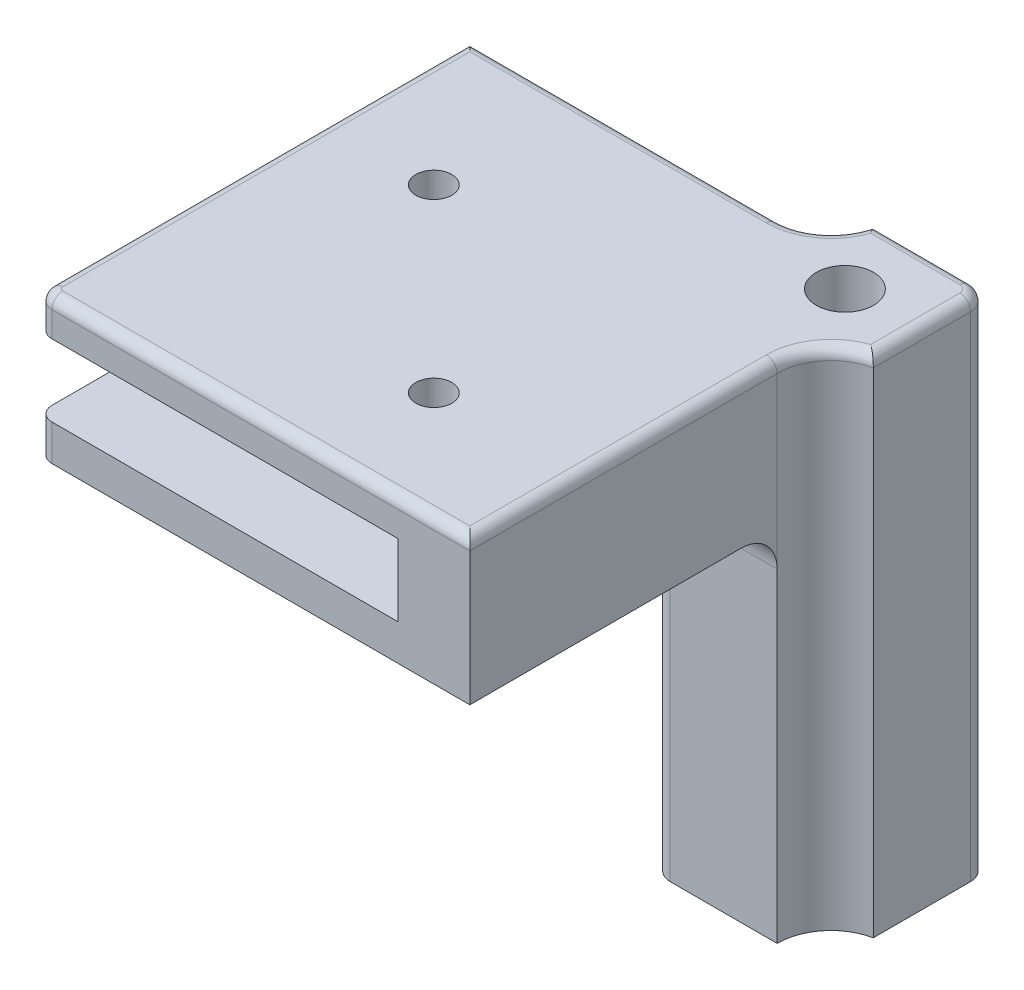
SolidWorks part; units mm, degrees
ref_plane "Front Plane" through (0, 0, 0) normal (0, 0, 1) x (1, 0, 0)
ref_plane "Top Plane" through (0, 0, 0) normal (0, 1, 0) x (1, 0, 0)
ref_plane "Right Plane" through (0, 0, 0) normal (1, 0, 0) x (0, 0, -1)
sketch "Sketch1" plane through (0, 0, 0) normal (0, 1, 0) x (1, 0, 0)
  line L1 (0, 0) -> (76.2, 0)
  line L2 (0, 0) -> (0, 76.2)
  line L3 (0, 76.2) -> (76.2, 76.2)
  line L4 (76.2, 0) -> (76.2, 76.2)
  dimension "D1" = 76.2
  dimension "D2" = 76.2
extrude "Boss-Extrude1" add sketch "Sketch1" along normal mid plane 25.4
sketch "Sketch3" plane through (0, 0, 0) normal (0, 1, 0) x (1, 0, 0)
  line L1 (63.5, 63.5) -> (0, 63.5)
  line L2 (63.5, 63.5) -> (63.5, 0)
  line L3 (63.5, 0) -> (0, 0)
  line L4 (0, 63.5) -> (0, 0)
  dimension "D1" = 63.5
  dimension "D2" = 63.5
extrude "Cut-Extrude1" cut sketch "Sketch3" against normal mid plane 12.7
sketch "Sketch4" plane through (0, 0, 0) normal (0, 1, 0) x (1, 0, 0)
  line L6 (76.2, 0) -> (76.2, 76.2) construction
  line L10 (0, 76.2) -> (0, 0)
  line L11 (0, 0) -> (76.2, 0)
  line L12 (76.2, 0) -> (76.2, 76.2)
  line L13 (76.2, 76.2) -> (0, 76.2)
  line L14 (0, 76.2) -> (0, 0) construction
  line L15 (0, 0) -> (76.2, 0) construction
  line L19 (76.2, 76.2) -> (0, 76.2) construction
  line L21 (63.5, 63.5) -> (83.82, 63.5)
  line L22 (63.5, 63.5) -> (63.5, 83.82)
  line L23 (63.5, 83.82) -> (83.82, 83.82)
  line L24 (83.82, 63.5) -> (83.82, 83.82)
  circle A2 centre (71.1581, 71.1581) radius 5.0419
  dimension "D1" = 10.0838
  dimension "D2" = 20.32
  dimension "D3" = 20.32
  dimension "D8" = 0
extrude "Boss-Extrude2" add sketch "Sketch4" along normal mid plane 25.4 contours L21 L24 L23 L22 A2 region at (63.7874, 0, -80.01) region at (67.329, 0, -76.0204) region at (75.0738, 0, -75.0738)
extrude "Cut-Extrude2" cut sketch "Sketch4<3>" against normal through all and the other way through all contours A2
sketch "Sketch4<3>" plane through (0, 0, 0) normal (0, 1, 0) x (1, 0, 0) same geometry as "Sketch4"
fillet "Fillet2" radius 9.525 2 edges at (63.5, 0, -76.2) (76.2, 0, -63.5)
fillet "Fillet3" radius 3.175 1 edges at (83.82, 0, -83.82)
sketch "Sketch5" plane through (0, 12.7, 0) normal (0, 1, 0) x (1, 0, 0)
  line L0 (0, 0) -> (76.2, 0) construction
  line L1 (0, 76.2) -> (0, 0) construction
  line L2 (54.1674, 76.2) -> (0, 76.2) construction
  line L3 (76.2, 0) -> (76.2, 54.1674) construction
  circle A0 centre (19.05, 50.8) radius 3.175
  circle A1 centre (50.8, 19.05) radius 3.175
  dimension "D1" = 6.35
  dimension "D2" = 19.05
  dimension "D3" = 19.05
  dimension "D4" = 25.4
  dimension "D5" = 25.4
extrude "Cut-Extrude3" cut sketch "Sketch5" against normal up to next
sketch "Sketch6" plane through (0, -12.7, 0) normal (0, -1, 0) x (1, 0, 0)
  line L0 (54.1674, -76.2) -> (54.1674, -54.1674)
  line L1 (54.1674, -54.1674) -> (76.2, -54.1674)
  line L6 (63.5, -83.82) -> (80.645, -83.82)
  line L7 (83.82, -80.645) -> (83.82, -63.5)
  line L8 (76.2, -54.1674) -> (76.2, 0)
  line L9 (76.2, 0) -> (0, 0)
  line L10 (0, 0) -> (0, -76.2)
  line L11 (0, -76.2) -> (54.1674, -76.2)
  line L12 (63.5, -83.82) -> (80.645, -83.82)
  line L13 (83.82, -80.645) -> (83.82, -63.5)
  circle A0 centre (71.1581, -71.1581) radius 5.0419 construction
  circle A1 centre (71.1581, -71.1581) radius 5.0419
  arc A5 (80.645, -83.82) -> (83.82, -80.645) centre (80.645, -80.645) ccw
  arc A6 (76.2, -54.1674) -> (83.82, -63.5) centre (85.725, -54.1674) ccw
  arc A7 (63.5, -83.82) -> (54.1674, -76.2) centre (54.1674, -85.725) ccw
  arc A8 (80.645, -83.82) -> (83.82, -80.645) centre (80.645, -80.645) ccw
  arc A9 (76.2, -54.1674) -> (83.82, -63.5) centre (85.725, -54.1674) ccw
  arc A10 (63.5, -83.82) -> (54.1674, -76.2) centre (54.1674, -85.725) ccw
  dimension "D1" = 0
extrude "Boss-Extrude3" add sketch "Sketch6" along normal blind 63.5
sketch "Sketch7" plane through (0, -76.2, 0) normal (0, -1, 0) x (1, 0, 0)
  line L0 (71.1581, -71.1581) -> (71.1581, -62.3593) construction
  line L1 (71.1581, -79.9569) -> (78.7781, -75.5575)
  line L2 (78.7781, -75.5575) -> (78.7781, -66.7587)
  line L3 (78.7781, -66.7587) -> (71.1581, -62.3593)
  line L4 (71.1581, -62.3593) -> (63.5381, -66.7587)
  line L5 (63.5381, -66.7587) -> (63.5381, -75.5575)
  line L6 (63.5381, -75.5575) -> (71.1581, -79.9569)
  circle A0 centre (71.1581, -71.1581) radius 7.62 construction
  dimension "D1" = 15.24
extrude "Cut-Extrude4" cut sketch "Sketch7" against normal blind 9.525
fillet "Fillet4" radius 3.175 1 edges at (54.1674, -44.45, -54.1674)
fillet "Fillet5" radius 6.35 3 edges at (54.1674, -12.7, -66.7712) (55.0974, -12.7, -55.0974) (66.7712, -12.7, -54.1674)
fillet "Fillet6" radius 2.54 2 edges at (0, -9.525, 0) (0, 9.525, 0)
fillet "Fillet7" radius 1.905 10 edges at (83.82, 12.7, -72.0725) (82.8901, 12.7, -82.8901) (78.347, 12.7, -60.1916) (60.1916, 12.7, -78.347) (39.37, 12.7, 0) (0.7439, 12.7, -0.7439) (72.0725, 12.7, -83.82) (76.2, 12.7, -27.0837) (27.0837, 12.7, -76.2) (0, 12.7, -39.37)
